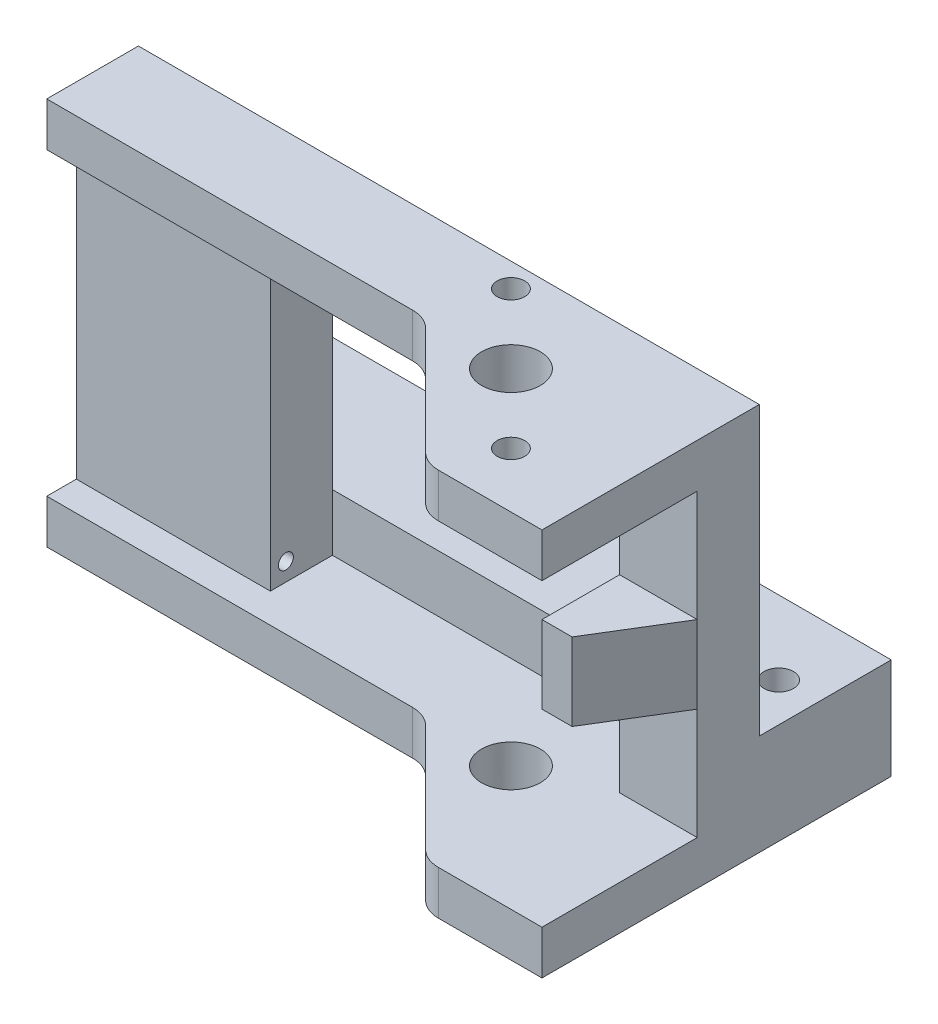
SolidWorks part; units mm, degrees
ref_plane "Front Plane" through (0, 0, 0) normal (0, 0, 1) x (1, 0, 0)
ref_plane "Top Plane" through (0, 0, 0) normal (0, 1, 0) x (1, 0, 0)
ref_plane "Right Plane" through (0, 0, 0) normal (1, 0, 0) x (0, 0, -1)
sketch "Sketch1" plane through (0, 0, 0) normal (0, 0, 1) x (1, 0, 0)
  line L1 (57.15, -31.75) -> (-57.15, -31.75)
  line L2 (57.15, -31.75) -> (57.15, 31.75)
  line L3 (57.15, 31.75) -> (-57.15, 31.75)
  line L4 (-57.15, -31.75) -> (-57.15, 31.75)
  line L5 (57.15, -31.75) -> (-57.15, 31.75) construction
  line L6 (57.15, 31.75) -> (-57.15, -31.75) construction
  point P0 (0, 0)
  dimension "D1" = 63.5
  dimension "D2" = 114.3
extrude "Boss-Extrude1" add sketch "Sketch1" along normal blind 57.15
sketch "Sketch2" plane through (0, 0, 57.15) normal (0, 0, 1) x (1, 0, 0)
  line L0 (-57.15, 31.75) -> (-57.15, -31.75) construction
  line L1 (57.15, -24.55) -> (-57.15, -24.55)
  line L2 (57.15, -24.55) -> (57.15, 24.55)
  line L3 (57.15, 24.55) -> (-57.15, 24.55)
  line L4 (-57.15, -24.55) -> (-57.15, 24.55)
  line L5 (57.15, -24.55) -> (-57.15, 24.55) construction
  line L6 (57.15, 24.55) -> (-57.15, -24.55) construction
  line L7 (57.15, 31.75) -> (-57.15, 31.75) construction
  point P0 (0, 0)
  dimension "D1" = 7.2
extrude "Cut-Extrude2" cut sketch "Sketch2" against normal blind 25.4
sketch "Sketch3" plane through (0, 0, 0) normal (0, 0, -1) x (-1, 0, 0)
  line L0 (-57.15, -31.75) -> (-57.15, 31.75) construction
  line L1 (57.15, 31.75) -> (-57.15, 31.75)
  line L2 (57.15, 31.75) -> (57.15, -15.24)
  line L3 (57.15, -15.24) -> (-57.15, -15.24)
  line L4 (-57.15, 31.75) -> (-57.15, -15.24)
  dimension "D1" = 46.99
extrude "Cut-Extrude3" cut sketch "Sketch3" against normal blind 21.59
sketch "Sketch5" plane through (0, -31.75, 0) normal (0, -1, 0) x (1, 0, 0)
  line L0 (0, 12.06) -> (50.8, 12.06) construction
  line L1 (57.15, 21.59) -> (-57.15, 21.59) construction
  line L2 (57.15, 57.15) -> (57.15, 0) construction
  circle A0 centre (0, 12.06) radius 2.415
  circle A1 centre (50.8, 12.06) radius 2.415
  dimension "D3" = 4.83
  dimension "D4" = 6.35
  dimension "D1" = 9.53
  dimension "D2" = 50.8
extrude "Cut-Extrude4" cut sketch "Sketch5" against normal blind 25.4
sketch "Sketch6" plane through (0, 0, 21.59) normal (0, 0, -1) x (-1, 0, 0)
  line L0 (-53.215, -15.24) -> (2.415, -15.24) construction
  line L1 (-53.215, -15.24) -> (-53.215, -31.75) construction
  line L2 (2.415, -31.75) -> (2.415, -15.24) construction
  line L3 (-57.15, -15.24) -> (57.15, -15.24) construction
  circle A1 centre (-5.08, -1.524) radius 2.2225
  dimension "D3" = 4.445
extrude "Cut-Extrude5" cut sketch "Sketch6" against normal blind 5.08
sketch "Sketch7" plane through (0, -31.75, 0) normal (0, -1, 0) x (1, 0, 0)
  line L0 (57.15, 57.15) -> (57.15, 0) construction
  line L2 (-57.15, 31.75) -> (57.15, 31.75) construction
  circle A0 centre (31.75, 36.83) radius 4.8
  dimension "D1" = 9.6
  dimension "D2" = 25.4
  dimension "D3" = 5.08
extrude "Cut-Extrude6" cut sketch "Sketch7" against normal up to surface (63.5 mm away) up to face at (0, 31.75, 39.37)
sketch "Sketch8" plane through (0, 31.75, 0) normal (0, 1, 0) x (1, 0, 0)
  line L0 (20.4363, -25.5163) -> (43.0637, -48.1437) construction
  line L1 (57.15, -31.75) -> (-57.15, -31.75) construction
  circle A0 centre (31.75, -36.83) radius 16 construction
  circle A1 centre (20.4363, -25.5163) radius 2.25
  circle A2 centre (43.0637, -48.1437) radius 2.25
  dimension "D1" = 32
  dimension "D2" = 4.5
  dimension "D3" = 45
sketch "Sketch9" plane through (0, 0, 31.75) normal (0, 0, 1) x (1, 0, 0)
  line L0 (57.15, 31.75) -> (-57.15, 31.75) construction
  line L5 (57.15, 24.55) -> (-57.15, 24.55) construction
  line L6 (-12.7, 24.55) -> (44.45, 24.55)
  line L7 (-12.7, 24.55) -> (-12.7, -24.55)
  line L8 (-12.7, -24.55) -> (44.45, -24.55)
  line L9 (44.45, 24.55) -> (44.45, -24.55)
  line L10 (-57.15, -24.55) -> (57.15, -24.55) construction
  line L11 (-57.15, 24.55) -> (-57.15, -24.55) construction
  line L12 (57.15, -24.55) -> (57.15, 24.55) construction
  line L13 (-57.15, -31.75) -> (-44.45, -31.75)
  line L14 (-57.15, -31.75) -> (-57.15, 31.75)
  line L15 (-57.15, 31.75) -> (-44.45, 31.75)
  line L16 (-44.45, -31.75) -> (-44.45, 31.75)
  line L17 (-57.15, -31.75) -> (-44.45, 31.75) construction
  line L18 (-57.15, 31.75) -> (-44.45, -31.75) construction
  line L19 (-57.15, -31.75) -> (57.15, -31.75) construction
  point P5 (-50.8, 0)
  dimension "D1" = 12.7
  dimension "25in" = 44.45
  dimension "D2" = 12.7
extrude "Cut-Extrude7" cut sketch "Sketch9" against normal through all both and the other way through all
extrude "Cut-Extrude8" cut sketch "Sketch8" against normal up to next
sketch "Sketch10" [suppressed] plane through (0, 0, 29.21) normal (0, 0, 1) x (1, 0, 0)
  line L1 (-30.607, -1.778) -> (-30.607, -6.604) construction
  circle A0 centre (-33.2489, -4.191) radius 2.286
  point P5 (-30.607, -4.191)
  dimension "D1" = 4.572
sketch "Sketch11" [suppressed] plane through (0, 0, 21.59) normal (0, 0, -1) x (-1, 0, 0)
  circle A0 centre (33.2489, -4.191) radius 2.286
  dimension "D1" = 4.572
extrude "Cut-Extrude9" [suppressed] cut sketch "Sketch11" against normal blind 3.81
sketch "Sketch12" plane through (-12.7, 0, 0) normal (1, 0, 0) x (0, 0, -1)
  line L0 (-31.75, -24.55) -> (-31.75, 24.55) construction
  line L1 (-29.21, -21.59) -> (-29.21, 21.59) construction
  line L2 (-21.59, 24.55) -> (-21.59, -15.24) construction
  circle A0 centre (-29.21, -21.59) radius 1.225
  circle A1 centre (-29.21, 21.59) radius 1.225
  point P0 (-31.75, 0)
  point P8 (-29.21, 0)
  dimension "D1" = 2.45
  dimension "D2" = 7.62
  dimension "D3" = 43.18
extrude "Cut-Extrude10" cut sketch "Sketch12" against normal up to surface (31.75 mm away) up to face at (-44.45, -3.048, 33.528)
sketch "Sketch13" plane through (0, 31.75, 0) normal (0, 1, 0) x (1, 0, 0)
  line L0 (-44.45, -36.5854) -> (17.5354, -36.5854)
  line L1 (17.5354, -36.5854) -> (38.1, -57.15)
  line L2 (57.15, -57.15) -> (-44.45, -57.15) construction
  line L3 (43.0637, -48.1437) -> (20.4363, -25.5163) construction
  line L4 (-44.45, -36.5854) -> (-44.45, -57.15)
  line L5 (-44.45, -57.15) -> (38.1, -57.15)
  line L6 (-44.45, -21.59) -> (-44.45, -57.15) construction
extrude "Cut-Extrude12" cut sketch "Sketch13" against normal through all
fillet "Fillet1" radius 5.08 4 edges at (38.1, -28.15, 57.15) (38.1, 28.15, 57.15) (17.5354, 28.15, 36.5854) (17.5354, -28.15, 36.5854)
sketch "Sketch14" plane through (44.45, 0, 0) normal (-1, 0, 0) x (0, 0, 1)
  line L0 (0, -24.55) -> (31.75, -24.55) construction
  line L1 (21.59, -15.24) -> (0, -15.24)
  line L2 (21.59, -15.24) -> (21.59, -24.55)
  line L3 (21.59, -24.55) -> (0, -24.55)
  line L4 (0, -15.24) -> (0, -24.55)
extrude "Boss-Extrude2" add sketch "Sketch14" along normal up to next
sketch "Sketch15" plane through (0, 0, 21.59) normal (0, 0, -1) x (-1, 0, 0)
  line L1 (17.907, -4.064) -> (17.907, 0.762) construction
  line L2 (17.907, 0.762) -> (32.893, 0.762) construction
  line L3 (22.2778, 0.762) -> (22.2778, -4.064) construction
  line L4 (27.813, -4.064) -> (17.907, -4.064) construction
  circle A0 centre (20.157, -1.651) radius 2.25
  point P4 (22.2778, -1.651)
  dimension "D1" = 4.5
extrude "Cut-Extrude13" cut sketch "Sketch15" against normal blind 5.08
sketch "Sketch16" plane through (0, 0, 31.75) normal (0, 0, 1) x (1, 0, 0)
  line L0 (44.45, -24.55) -> (44.45, 24.55) construction
  line L1 (57.15, -6.35) -> (44.45, -6.35)
  line L2 (57.15, -6.35) -> (57.15, 6.35)
  line L3 (57.15, 6.35) -> (44.45, 6.35)
  line L4 (44.45, -6.35) -> (44.45, 6.35)
  line L5 (57.15, -6.35) -> (44.45, 6.35) construction
  line L6 (57.15, 6.35) -> (44.45, -6.35) construction
  line L7 (57.15, 6.35) -> (57.15, -6.35) construction
  line L9 (57.15, -24.55) -> (57.15, 24.55) construction
  point P0 (50.8, 0)
  point P7 (57.15, 0)
  point P8 (0, 0)
  dimension "D1" = 12.7
extrude "Boss-Extrude3" add sketch "Sketch16" along normal blind 12.7
sketch "Sketch17" plane through (0, 6.35, 0) normal (0, 1, 0) x (1, 0, 0)
  line L0 (49.375, -44.45) -> (57.15, -31.75)
  line L1 (57.15, -44.45) -> (57.15, -31.75) construction
  line L2 (57.15, -31.75) -> (44.45, -31.75) construction
  line L3 (57.15, -31.75) -> (57.15, -44.45)
  line L4 (57.15, -44.45) -> (49.375, -44.45)
  line L5 (57.15, -44.45) -> (44.45, -44.45) construction
extrude "Cut-Extrude14" cut sketch "Sketch17" against normal blind 12.7
